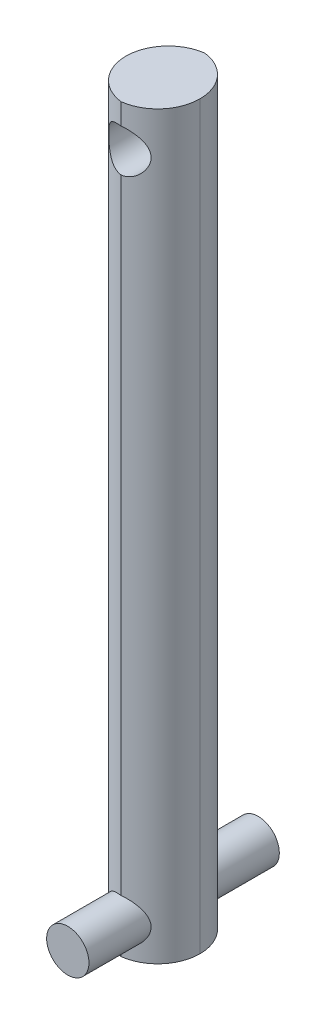
SolidWorks part; units mm, degrees
material "Hexcel AS4C (3000 Filaments)"
ref_plane "Front Plane" through (0, 0, 0) normal (0, 0, 1) x (1, 0, 0)
ref_plane "Top Plane" through (0, 0, 0) normal (0, 1, 0) x (1, 0, 0)
ref_plane "Right Plane" through (0, 0, 0) normal (1, 0, 0) x (0, 0, -1)
sketch "Sketch2" plane through (0, 0, 0) normal (0, 1, 0) x (1, 0, 0)
  line L1 (-3.5, 4) -> (3.5, 4)
  line L2 (-3.5, 4) -> (-3.5, -4)
  line L3 (-3.5, -4) -> (3.5, -4)
  line L4 (3.5, 4) -> (3.5, -4)
  line L5 (-3.5, 4) -> (3.5, -4) construction
  line L6 (-3.5, -4) -> (3.5, 4) construction
  point P0 (0, 0)
  dimension "D1" = 8
  dimension "D2" = 7
extrude "Boss-Extrude1" add sketch "Sketch2" along normal blind 70
sketch "Sketch3" plane through (0, 0, 4) normal (0, 0, 1) x (1, 0, 0)
  line L0 (0, 0) -> (0, 70) construction
  line L1 (-3.5, 70) -> (3.5, 70) construction
  line L2 (-3.5, 3) -> (3.5, 3) construction
  line L3 (-3.5, 70) -> (-3.5, 0) construction
  line L4 (3.5, 70) -> (3.5, 0) construction
  line L5 (-3.5, 0) -> (3.5, 0) construction
  circle A0 centre (0, 3) radius 2
  dimension "D1" = 4
  dimension "D2" = 3
extrude "Boss-Extrude2" add sketch "Sketch3" along normal blind 5
mirror "Mirror1" about plane through (0, 0, 0) normal (0, 0, 1) of "Boss-Extrude2"
sketch "Sketch4" plane through (0, 0, 4) normal (0, 0, 1) x (1, 0, 0)
  line L0 (-3.5, 66) -> (3.5, 66) construction
  line L1 (-3.5, 70) -> (-3.5, 0) construction
  line L2 (3.5, 70) -> (3.5, 0) construction
  line L3 (-3.5, 70) -> (3.5, 70) construction
  circle A0 centre (0, 66) radius 2
  dimension "D2" = 4
  dimension "D1" = 4
extrude "Cut-Extrude1" cut sketch "Sketch4" against normal up to next
fillet "Fillet1" radius 4 4 edges at (-3.5, 35, 4) (-3.5, 35, -4) (3.5, 35, -4) (3.5, 35, 4)
